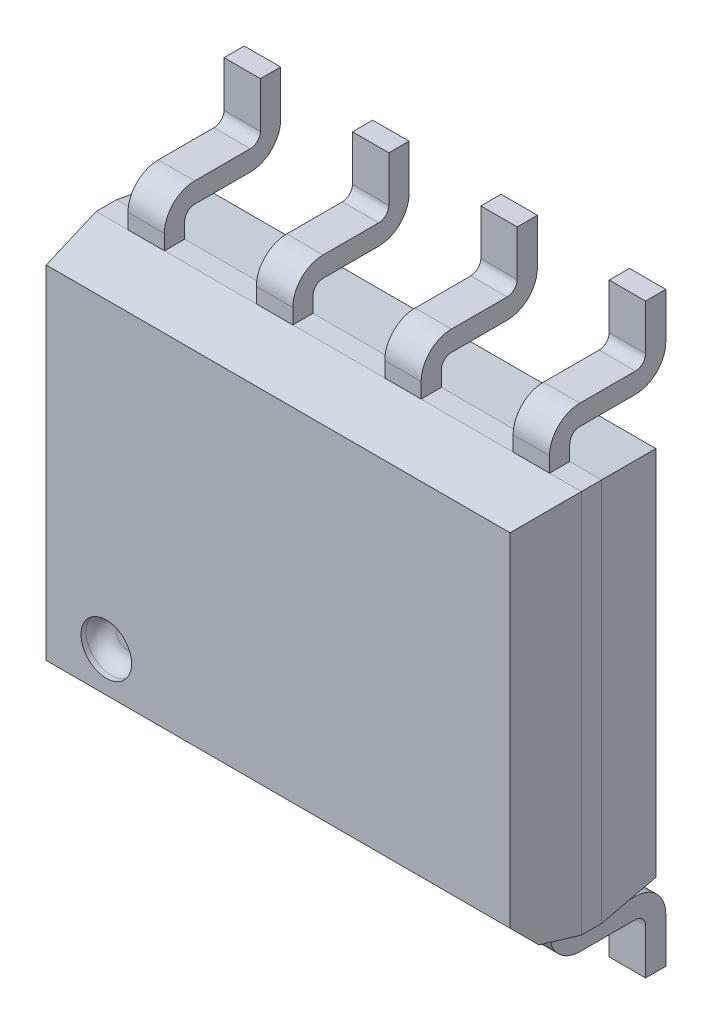
SolidWorks part; units mm, degrees
ref_plane "Płaszczyzna przednia" through (0, 0, 0) normal (0, 0, 1) x (1, 0, 0)
ref_plane "Płaszczyzna górna" through (0, 0, 0) normal (0, 1, 0) x (1, 0, 0)
ref_plane "Płaszczyzna prawa" through (0, 0, 0) normal (1, 0, 0) x (0, 0, -1)
sketch "Szkic1" plane through (0, 0, 0) normal (0, 0, 1) x (1, 0, 0)
  line L1 (0, 0) -> (2.4, 0)
  line L2 (0, 0) -> (0, 1.9)
  line L3 (0, 1.9) -> (2.4, 1.9)
  line L4 (2.4, 0) -> (2.4, 1.9)
  dimension "D1" = 2.4
  dimension "D2" = 1.9
extrude "Wyciągnięcie1" add sketch "Szkic1" along normal blind 1.75
sketch "Szkic2" plane through (0, 0, 0) normal (0, -1, 0) x (1, 0, 0)
  line L1 (0, 0) -> (2.4, 0)
  line L2 (0, 0) -> (0, 1.75)
  line L3 (0, 1.75) -> (2.4, 1.75)
  line L4 (2.4, 0) -> (2.4, 1.75)
extrude "Wyciągnięcie2" add sketch "Szkic2" along normal blind 1.9
sketch "Szkic3" plane through (0, 0, 0) normal (-1, 0, 0) x (0, 0, 1)
  line L1 (0, 1.9) -> (1.75, 1.9)
  line L2 (0, 1.9) -> (0, -1.9)
  line L3 (0, -1.9) -> (1.75, -1.9)
  line L4 (1.75, 1.9) -> (1.75, -1.9)
extrude "Wyciągnięcie3" add sketch "Szkic3" along normal blind 2.4
chamfer "Sfazowanie1" distance 0.6 angle 10 1 edges at (0, -1.9, 1.75) first distance on face at (0, -1.9, 0.875)
chamfer "Sfazowanie3" distance 0.2 angle 45 1 edges at (0, -1.7942, 1.75) first distance on face at (0, 0.0529, 1.75)
chamfer "Sfazowanie4" distance 0.6 angle 10 1 edges at (0, 1.9, 1.75) first distance on face at (0, 1.9, 0.875)
sketch "Szkic4" plane through (0, -1.9, 0) normal (0, -1, 0) x (1, 0, 0)
  line L0 (2.4, 1.15) -> (-2.4, 1.15) construction
  line L1 (-2.085, 1.15) -> (-1.725, 1.15)
  line L2 (-2.085, 1.15) -> (-2.085, 0.95)
  line L3 (-2.085, 0.95) -> (-1.725, 0.95)
  line L4 (-1.725, 1.15) -> (-1.725, 0.95)
  line L6 (-0.815, 1.15) -> (-0.455, 1.15)
  line L7 (-0.815, 1.15) -> (-0.815, 0.95)
  line L8 (-0.815, 0.95) -> (-0.455, 0.95)
  line L9 (-0.455, 1.15) -> (-0.455, 0.95)
  line L10 (0.455, 1.15) -> (0.815, 1.15)
  line L11 (0.455, 1.15) -> (0.455, 0.95)
  line L12 (0.455, 0.95) -> (0.815, 0.95)
  line L13 (0.815, 1.15) -> (0.815, 0.95)
  line L14 (1.725, 1.15) -> (2.085, 1.15)
  line L15 (1.725, 1.15) -> (1.725, 0.95)
  line L16 (1.725, 0.95) -> (2.085, 0.95)
  line L17 (2.085, 1.15) -> (2.085, 0.95)
  dimension "D1" = 0.36
  dimension "D2" = 0.36
  dimension "D3" = 0.91
  dimension "D4" = 0.91
  dimension "D5" = 0.36
  dimension "D6" = 0.455
  dimension "D7" = 0.91
  dimension "D8" = 0.36
  dimension "D9" = 0.2
  dimension "D10" = 0.2
  dimension "D11" = 0.2
  dimension "D12" = 0.2
extrude "Wyciągnięcie4" add sketch "Szkic4" along normal blind 0.45
sketch "Szkic6" plane through (0, 0, 0.95) normal (0, 0, -1) x (-1, 0, 0)
  line L0 (-1.725, -2.35) -> (-1.725, -1.9) construction
  line L1 (-2.085, -2.35) -> (-1.725, -2.35)
  line L2 (-2.085, -2.35) -> (-2.085, -2.15)
  line L3 (-2.085, -2.15) -> (-1.725, -2.15)
  line L4 (-1.725, -2.35) -> (-1.725, -2.15)
  line L5 (-0.455, -2.35) -> (-0.455, -1.9) construction
  line L6 (-0.815, -2.35) -> (-0.455, -2.35)
  line L7 (-0.815, -2.35) -> (-0.815, -2.15)
  line L8 (-0.815, -2.15) -> (-0.455, -2.15)
  line L9 (-0.455, -2.35) -> (-0.455, -2.15)
  line L10 (0.815, -2.35) -> (0.815, -1.9) construction
  line L11 (0.455, -2.35) -> (0.815, -2.35)
  line L12 (0.455, -2.35) -> (0.455, -2.15)
  line L13 (0.455, -2.15) -> (0.815, -2.15)
  line L14 (0.815, -2.35) -> (0.815, -2.15)
  line L15 (2.085, -2.35) -> (2.085, -1.9) construction
  line L16 (1.725, -2.35) -> (2.085, -2.35)
  line L17 (1.725, -2.35) -> (1.725, -2.15)
  line L18 (1.725, -2.15) -> (2.085, -2.15)
  line L19 (2.085, -2.35) -> (2.085, -2.15)
  dimension "D1" = 0.2
  dimension "D2" = 0.2
  dimension "D3" = 0.2
  dimension "D4" = 0.2
extrude "Wyciągnięcie5" add sketch "Szkic6" along normal blind 0.95
sketch "Szkic10" plane through (0, 1.9, 0) normal (0, 1, 0) x (-1, 0, 0)
  line L0 (2.4, 1.15) -> (-2.4, 1.15) construction
  line L1 (2.085, 1.15) -> (1.725, 1.15)
  line L2 (2.085, 1.15) -> (2.085, 0.95)
  line L3 (2.085, 0.95) -> (1.725, 0.95)
  line L4 (1.725, 1.15) -> (1.725, 0.95)
  line L6 (0.815, 1.15) -> (0.455, 1.15)
  line L7 (0.815, 1.15) -> (0.815, 0.95)
  line L8 (0.815, 0.95) -> (0.455, 0.95)
  line L9 (0.455, 1.15) -> (0.455, 0.95)
  line L10 (-0.455, 1.15) -> (-0.815, 1.15)
  line L11 (-0.455, 1.15) -> (-0.455, 0.95)
  line L12 (-0.455, 0.95) -> (-0.815, 0.95)
  line L13 (-0.815, 1.15) -> (-0.815, 0.95)
  line L14 (-1.725, 1.15) -> (-2.085, 1.15)
  line L15 (-1.725, 1.15) -> (-1.725, 0.95)
  line L16 (-1.725, 0.95) -> (-2.085, 0.95)
  line L17 (-2.085, 1.15) -> (-2.085, 0.95)
  dimension "D1" = 0.36
  dimension "D2" = 0.91
  dimension "D3" = 0.36
  dimension "D4" = 0.2
  dimension "D5" = 0.2
  dimension "D6" = 0.36
  dimension "D7" = 0.2
  dimension "D8" = 0.91
  dimension "D9" = 0.36
  dimension "D10" = 0.2
  dimension "D11" = 0.91
  dimension "D12" = 0.455
extrude "Wyciągnięcie6" add sketch "Szkic10" along normal blind 0.45
sketch "Szkic11" plane through (0, 0, 0.95) normal (0, 0, -1) x (-1, 0, 0)
  line L0 (-1.725, 2.35) -> (-1.725, 1.9) construction
  line L1 (-2.085, 2.35) -> (-1.725, 2.35)
  line L2 (-2.085, 2.35) -> (-2.085, 2.15)
  line L3 (-2.085, 2.15) -> (-1.725, 2.15)
  line L4 (-1.725, 2.35) -> (-1.725, 2.15)
  line L5 (-0.455, 2.35) -> (-0.455, 1.9) construction
  line L6 (-0.815, 2.35) -> (-0.455, 2.35)
  line L7 (-0.815, 2.35) -> (-0.815, 2.15)
  line L8 (-0.815, 2.15) -> (-0.455, 2.15)
  line L9 (-0.455, 2.35) -> (-0.455, 2.15)
  line L10 (0.815, 2.35) -> (0.815, 1.9) construction
  line L11 (0.455, 2.35) -> (0.815, 2.35)
  line L12 (0.455, 2.35) -> (0.455, 2.15)
  line L13 (0.455, 2.15) -> (0.815, 2.15)
  line L14 (0.815, 2.35) -> (0.815, 2.15)
  line L15 (2.085, 2.35) -> (2.085, 1.9) construction
  line L16 (1.725, 2.35) -> (2.085, 2.35)
  line L17 (1.725, 2.35) -> (1.725, 2.15)
  line L18 (1.725, 2.15) -> (2.085, 2.15)
  line L19 (2.085, 2.35) -> (2.085, 2.15)
  dimension "D1" = 0.2
  dimension "D2" = 0.2
  dimension "D3" = 0.2
  dimension "D4" = 0.2
extrude "Wyciągnięcie7" add sketch "Szkic11" along normal blind 0.95
sketch "Szkic12" plane through (0, 0, 0) normal (0, 0, -1) x (-1, 0, 0)
  line L1 (-2.4, 1.9) -> (2.4, 1.9)
  line L2 (-2.4, 1.9) -> (-2.4, -1.9)
  line L3 (-2.4, -1.9) -> (2.4, -1.9)
  line L4 (2.4, 1.9) -> (2.4, -1.9)
extrude "Wytnij-wyciągnięcie3" cut sketch "Szkic12" against normal blind 0.35
chamfer "Sfazowanie6" distance 0.6 angle 6 1 edges at (0, -1.9, 0.35) first distance on face at (0.084, -1.9, 0.99)
chamfer "Sfazowanie7" distance 0.6 angle 6 1 edges at (2.4, 0.0315, 0.35) first distance on face at (2.4, -0.4342, 1.1196)
chamfer "Sfazowanie8" distance 0.6 angle 6 1 edges at (-0.0315, 1.9, 0.35) first distance on face at (0.0313, 1.9, 0.9881)
chamfer "Sfazowanie9" distance 0.6 angle 6 1 edges at (-2.4, 0, 0.35) first distance on face at (-2.4, -0.1819, 1.1008)
chamfer "Sfazowanie10" distance 0.6 angle 10 1 edges at (-2.4, 0.1, 1.75) first distance on face at (-2.4, -0.2339, 1.3153)
chamfer "Sfazowanie11" distance 0.6 angle 10 1 edges at (2.4, 0.1, 1.75) first distance on face at (2.4, -0.2339, 1.3153)
sketch "Szkic13" plane through (0, 2.35, 0) normal (0, 1, 0) x (-1, 0, 0)
  line L0 (1.725, 1.15) -> (1.725, 0) construction
  line L1 (2.085, 0) -> (1.725, 0)
  line L2 (2.085, 0) -> (2.085, 0.2)
  line L3 (2.085, 0.2) -> (1.725, 0.2)
  line L4 (1.725, 0) -> (1.725, 0.2)
  line L5 (0.455, 1.15) -> (0.455, 0) construction
  line L6 (0.815, 0) -> (0.455, 0)
  line L7 (0.815, 0) -> (0.815, 0.2)
  line L8 (0.815, 0.2) -> (0.455, 0.2)
  line L9 (0.455, 0) -> (0.455, 0.2)
  line L10 (-0.815, 1.15) -> (-0.815, 0) construction
  line L11 (-0.455, 0) -> (-0.815, 0)
  line L12 (-0.455, 0) -> (-0.455, 0.2)
  line L13 (-0.455, 0.2) -> (-0.815, 0.2)
  line L14 (-0.815, 0) -> (-0.815, 0.2)
  line L15 (-2.085, 1.15) -> (-2.085, 0) construction
  line L16 (-1.725, 0) -> (-2.085, 0)
  line L17 (-1.725, 0) -> (-1.725, 0.2)
  line L18 (-1.725, 0.2) -> (-2.085, 0.2)
  line L19 (-2.085, 0) -> (-2.085, 0.2)
  dimension "D1" = 0.2
  dimension "D2" = 0.2
  dimension "D3" = 0.2
  dimension "D4" = 0.2
extrude "Wyciągnięcie8" add sketch "Szkic13" along normal blind 0.55
sketch "Szkic14" plane through (0, -2.35, 0) normal (0, -1, 0) x (1, 0, 0)
  line L0 (-1.725, 0) -> (-1.725, 1.15) construction
  line L1 (-2.085, 0) -> (-1.725, 0)
  line L2 (-2.085, 0) -> (-2.085, 0.2)
  line L3 (-2.085, 0.2) -> (-1.725, 0.2)
  line L4 (-1.725, 0) -> (-1.725, 0.2)
  line L5 (-0.455, 0) -> (-0.455, 1.15) construction
  line L6 (-0.815, 0) -> (-0.455, 0)
  line L7 (-0.815, 0) -> (-0.815, 0.2)
  line L8 (-0.815, 0.2) -> (-0.455, 0.2)
  line L9 (-0.455, 0) -> (-0.455, 0.2)
  line L10 (0.815, 0) -> (0.815, 1.15) construction
  line L11 (0.455, 0) -> (0.815, 0)
  line L12 (0.455, 0) -> (0.455, 0.2)
  line L13 (0.455, 0.2) -> (0.815, 0.2)
  line L14 (0.815, 0) -> (0.815, 0.2)
  line L15 (2.085, 0) -> (2.085, 1.15) construction
  line L16 (1.725, 0) -> (2.085, 0)
  line L17 (1.725, 0) -> (1.725, 0.2)
  line L18 (1.725, 0.2) -> (2.085, 0.2)
  line L19 (2.085, 0) -> (2.085, 0.2)
  dimension "D1" = 0.2
  dimension "D2" = 0.2
  dimension "D3" = 0.2
  dimension "D4" = 0.2
extrude "Wyciągnięcie9" add sketch "Szkic14" along normal blind 0.55
fillet "Zaokrąglenie1" radius 0.3 1 edges at (-1.905, -2.35, 1.15)
fillet "Zaokrąglenie2" radius 0.3 1 edges at (-0.635, -2.35, 1.15)
fillet "Zaokrąglenie3" radius 0.3 1 edges at (0.635, -2.35, 1.15)
fillet "Zaokrąglenie4" radius 0.3 1 edges at (1.905, -2.35, 1.15)
fillet "Zaokrąglenie5" radius 0.1 1 edges at (-1.905, -2.15, 0.95)
fillet "Zaokrąglenie6" radius 0.3 1 edges at (1.905, -2.15, 0)
fillet "Zaokrąglenie7" radius 0.3 1 edges at (0.635, -2.15, 0)
fillet "Zaokrąglenie8" radius 0.3 1 edges at (-0.635, -2.15, 0)
fillet "Zaokrąglenie9" radius 0.3 1 edges at (-1.905, -2.15, 0)
fillet "Zaokrąglenie10" radius 0.3 1 edges at (1.905, 2.35, 1.15)
fillet "Zaokrąglenie11" radius 0.3 1 edges at (0.635, 2.35, 1.15)
fillet "Zaokrąglenie12" radius 0.3 1 edges at (-0.635, 2.35, 1.15)
fillet "Zaokrąglenie13" radius 0.3 1 edges at (-1.905, 2.35, 1.15)
fillet "Zaokrąglenie14" radius 0.3 1 edges at (-1.905, 2.15, 0)
fillet "Zaokrąglenie15" radius 0.3 1 edges at (-0.635, 2.15, 0)
fillet "Zaokrąglenie16" radius 0.3 1 edges at (0.635, 2.15, 0)
fillet "Zaokrąglenie17" radius 0.3 1 edges at (1.905, 2.15, 0)
fillet "Zaokrąglenie18" radius 0.1 1 edges
fillet "Zaokrąglenie19" radius 0.1 1 edges
fillet "Zaokrąglenie20" radius 0.1 1 edges
fillet "Zaokrąglenie21" radius 0.1 1 edges
fillet "Zaokrąglenie22" radius 0.1 1 edges at (-0.635, -2.15, 0.95)
fillet "Zaokrąglenie23" radius 0.1 1 edges at (0.635, -2.15, 0.95)
fillet "Zaokrąglenie24" radius 0.1 1 edges at (1.905, -2.15, 0.95)
fillet "Zaokrąglenie25" radius 0.1 1 edges at (-1.905, 2.15, 0.95)
fillet "Zaokrąglenie26" radius 0.1 1 edges at (-0.635, 2.15, 0.95)
fillet "Zaokrąglenie27" radius 0.1 1 edges at (0.635, 2.15, 0.95)
fillet "Zaokrąglenie28" radius 0.1 1 edges at (1.905, 2.15, 0.95)
fillet "Zaokrąglenie29" radius 0.1 1 edges
fillet "Zaokrąglenie30" radius 0.1 1 edges
fillet "Zaokrąglenie31" radius 0.1 1 edges
fillet "Zaokrąglenie32" radius 0.1 1 edges
sketch "Szkic15" plane through (0, 0, 1.75) normal (0, 0, 1) x (1, 0, 0)
  line L0 (-2.085, -1.9) -> (-2.4, -1.9) construction
  line L1 (-2.4, -1.9) -> (-2.4, 1.9) construction
  circle A0 centre (-1.7, -1.2) radius 0.25
  dimension "D1" = 0.5
  dimension "D2" = 0.7
  dimension "D3" = 0.7
extrude "Wytnij-wyciągnięcie4" cut sketch "Szkic15" against normal blind 0.2
fillet "Zaokrąglenie33" radius 0.15 1 edges at (-1.45, -1.2, 1.55)
